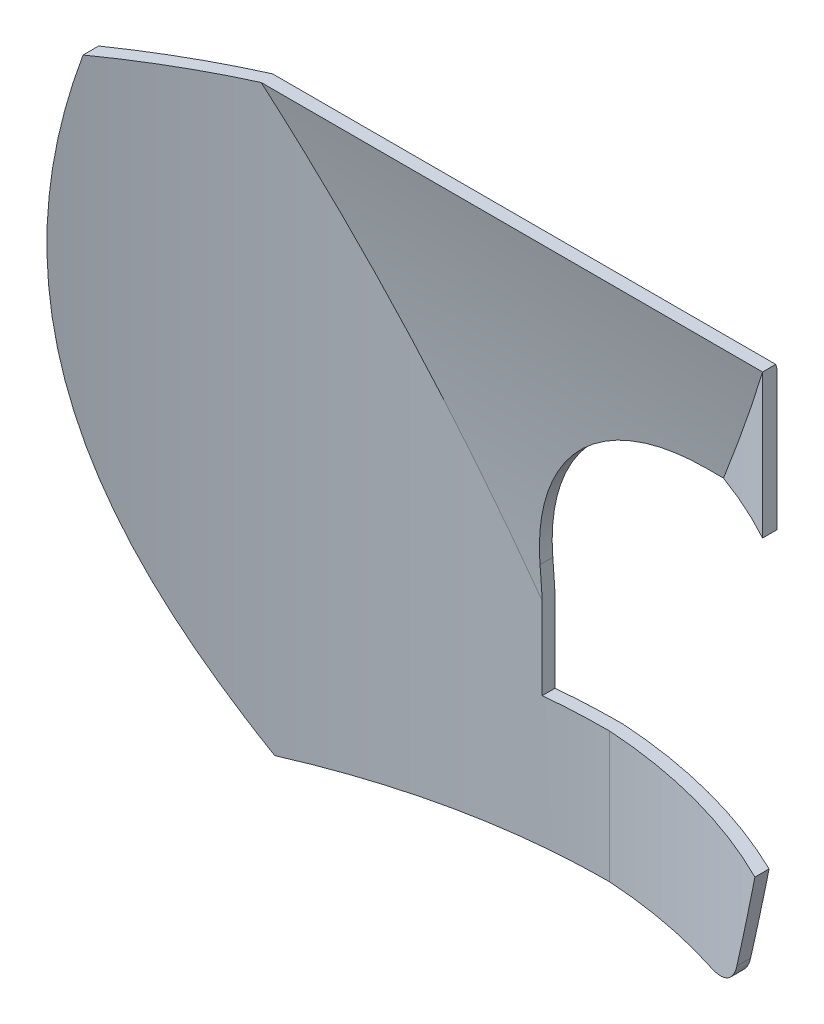
SolidWorks part; units mm, degrees
material "ABS"
ref_plane "Front Plane" through (0, 0, 0) normal (0, 0, 1) x (1, 0, 0)
ref_plane "Top Plane" through (0, 0, 0) normal (0, 1, 0) x (1, 0, 0)
ref_plane "Right Plane" through (0, 0, 0) normal (1, 0, 0) x (0, 0, -1)
sketch "Sketch1" plane through (0, 0, 0) normal (0, 0, 1) x (1, 0, 0)
  line L1 (0, 152.4) -> (152.4, 152.4)
  line L2 (0, 152.4) -> (0, 0)
  line L3 (0, 0) -> (152.4, 0)
  line L4 (152.4, 152.4) -> (152.4, 0)
  dimension "D1" = 152.4
extrude "Boss-Extrude1" add sketch "Sketch1" along normal blind 76.2
sketch "Sketch3" plane through (0, 0, 76.2) normal (0, 0, 1) x (1, 0, 0)
  line L0 (82.1057, 44.444) -> (82.1057, 64.764) construction
  line L1 (82.1057, 44.444) -> (132.9057, 44.444) construction
  line L2 (131.4198, 41.904) -> (124.7698, 21.6807)
  line L5 (117.6657, 100.324) -> (134.6523, 100.324) construction
  line L6 (136.9362, 101.6338) -> (140.9404, 108.4783) construction
  line L22 (132.9057, 44.444) -> (162.8642, 95.6522) construction
  line L25 (160.3111, 105.404) -> (150.6922, 111.0313) construction
  line L26 (134.6523, 102.9699) -> (117.029, 102.9699)
  line L27 (78.8231, 64.764) -> (78.8231, 41.904)
  line L28 (134.6523, 102.9699) -> (134.6523, 131.6857)
  line L29 (134.6523, 131.6857) -> (12.0396, 131.6857)
  line L32 (78.8231, 41.904) -> (131.4198, 41.904)
  line L35 (36.4349, 15.8356) -> (116.6948, 15.8356)
  arc A0 (82.1057, 64.764) -> (117.6657, 100.324) centre (117.6657, 64.764) cw construction
  arc A1 (134.6523, 100.324) -> (136.9362, 101.6338) centre (134.6523, 102.9699) ccw construction
  arc A2 (140.9404, 108.4783) -> (150.6922, 111.0313) centre (147.0928, 104.8789) cw construction
  arc A3 (162.8642, 95.6522) -> (160.3111, 105.404) centre (156.7118, 99.2515) ccw construction
  arc A4 (117.029, 102.9699) -> (78.8231, 64.764) centre (117.029, 64.764) ccw
  arc A5 (36.4349, 15.8356) -> (12.0396, 131.6857) centre (142.0774, 98.5751) cw
  arc A6 (116.6948, 15.8356) -> (124.7698, 21.6807) centre (116.6948, 24.336) ccw
  point P10 (138.9383, 105.056)
  dimension "D1" = 60.96
  dimension "D2" = 120.329
  dimension "D3" = 55.88
  dimension "D4" = 20.32
  dimension "D5" = 25.4
  dimension "D6" = 2.54
  dimension "D7" = 57.1898
  dimension "D8" = 50.8
  dimension "D9" = 64.0343
  dimension "D10" = 6.5653
  dimension "D11" = 80.2598
  dimension "D12" = 115.8501
  dimension "D13" = 28.7158
extrude "Cut-Extrude1" cut sketch "Sketch3" against normal blind 101.6 flip side to cut
sketch "Sketch5" plane through (0, 131.6857, 0) normal (0, 1, 0) x (1, 0, 0)
  line L1 (134.6523, 0) -> (12.0396, 0) construction
  line L2 (0.3818, -50.973) -> (0.3818, -34.7763)
  line L4 (134.6523, 0) -> (134.6523, -76.2) construction
  line L6 (134.6523, -45.8213) -> (134.6523, -12.4474)
  arc A0 (0.3818, -34.7763) -> (91.6661, 0) centre (91.6661, -137.1945) cw
  arc A1 (91.6661, 0) -> (134.6523, -12.4474) centre (85.2451, -102.6231) cw
  arc A9 (134.6523, -45.8213) -> (0.3818, -50.973) centre (67.4182, -45.8213) cw
extrude "Cut-Extrude2" cut sketch "Sketch5" against normal blind 178.816 flip side to cut
sketch "Sketch6" plane through (134.6523, 0, 0) normal (1, 0, 0) x (0, 0, -1)
  line L0 (-12.4474, 131.6857) -> (-45.8213, 131.6857)
  line L2 (-39.4975, 15.8356) -> (-4.3735, 15.8356)
  line L3 (-4.3735, 15.8356) -> (-13.084, -73.8763)
  line L4 (-13.084, -73.8763) -> (-142.7408, -65.9445)
  line L5 (-142.7408, -65.9445) -> (-120.0056, 200.4017)
  line L6 (-120.0056, 200.4017) -> (3.7687, 197.9585)
  line L9 (-4.727, 15.8356) -> (-76.2, 15.8356) construction
  line L10 (0, 15.8356) -> (0, 41.904) construction
  line L11 (-0.6025, 41.904) -> (-76.2, 41.904) construction
  line L12 (0, 41.904) -> (3.7687, 197.9585)
  arc A0 (-45.8213, 131.6857) -> (-50.3497, 90.4658) centre (-4.1347, 106.2473) ccw
  arc A1 (-50.3497, 90.4658) -> (-46.364, 60.554) centre (-123.4482, 65.5041) cw
  arc A2 (-46.364, 60.554) -> (-39.4975, 15.8356) centre (58.732, 53.8051) ccw
  arc A3 (-12.4474, 131.6857) -> (0, 41.904) centre (-368.2705, 36.6003) cw
extrude "Cut-Extrude4" cut sketch "Sketch6" against normal blind 178.816
sketch "Sketch16" plane through (0, 131.6857, 0) normal (0, 1, 0) x (1, 0, 0)
  line L3 (134.6523, -12.4474) -> (134.6523, -45.8213) construction
  line L4 (170.8957, -71.7893) -> (168.1749, -1.2953)
  line L5 (8.1099, -52.97) -> (134.2712, -52.97) construction
  line L6 (134.6523, -29.1344) -> (168.1749, -1.2953)
  arc A0 (134.6523, -29.1344) -> (112.3806, -43.4706) centre (118.9024, -29.1344) cw
  arc A1 (112.3806, -43.4706) -> (91.5076, -52.97) centre (106.0829, -57.3145) ccw
  arc A2 (91.5076, -52.97) -> (170.8957, -71.7893) centre (140.8088, -21.8525) ccw
extrude "Cut-Extrude12" cut sketch "Sketch16" against normal blind 44.196
shell "Shell6" thickness 2.54 removed face at (134.6523, 117.3278, 20.7909) removed face at (125.4777, 102.9699, 20.4052) removed face at (95.4581, 89.9474, 34.2086) removed face at (78.8231, 55.3657, 23.5158) removed face at (128.0928, 31.7863, 26.5888) removed face at (121.3651, 18.2291, 23.3887) removed face at (79.4938, 15.8356, 18.3363) removed face at (18.3238, 70.0787, 37.8438) removed face at (77.1012, 131.6857, 31.1101) removed face at (102.5377, 41.904, 20.2007) removed face at (101.3597, 116.141, 45.556) removed face at (123.2393, 114.3711, 39.8737) removed face at (58.4988, 109.5811, 49.9506) removed face at (53.0992, 71.653, 47.2443) removed face at (83.3038, 35.5381, 43.7919) outward yes
